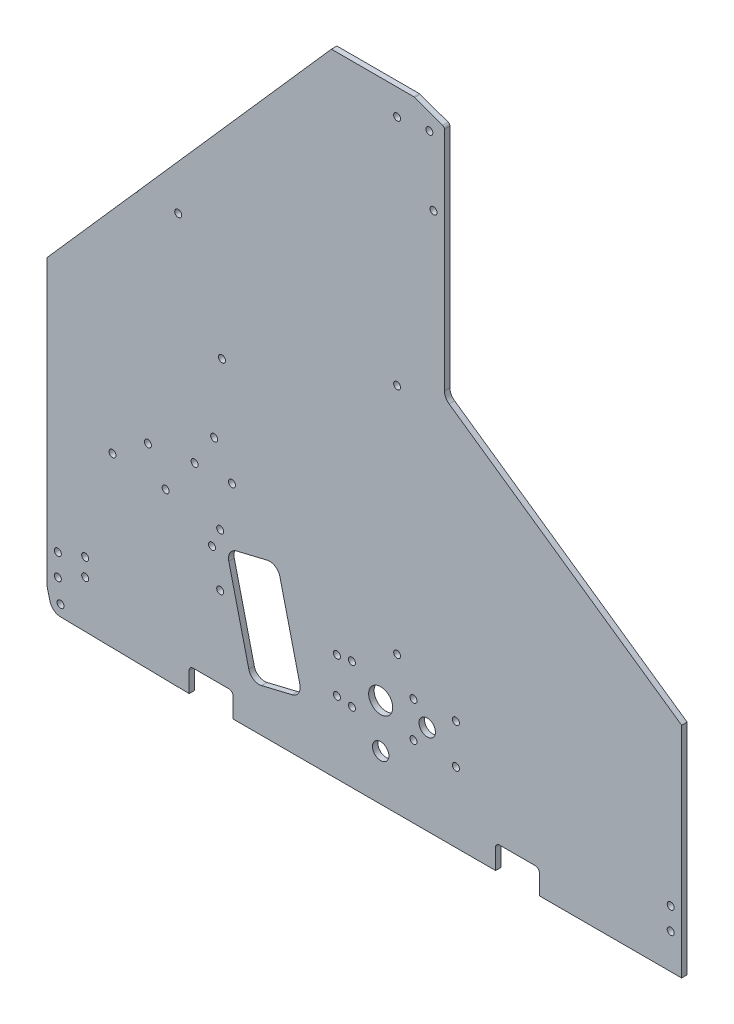
SolidWorks part; units mm, degrees
ref_plane "Front Plane" through (0, 0, 0) normal (0, 0, 1) x (1, 0, 0)
ref_plane "Top Plane" through (0, 0, 0) normal (0, 1, 0) x (1, 0, 0)
ref_plane "Right Plane" through (0, 0, 0) normal (1, 0, 0) x (0, 0, -1)
sketch "Sketch1" plane through (0, 0, 0) normal (0, 0, 1) x (1, 0, 0)
  line L0 (82.55, -20.32) -> (82.55, -6.35)
  line L2 (0, 0) -> (0, 157.48)
  line L4 (368.3, -20.32) -> (368.3, 106.68)
  line L5 (82.55, -6.35) -> (107.95, -6.35)
  line L6 (107.95, -6.35) -> (107.95, -20.32)
  line L7 (107.95, -20.32) -> (260.35, -20.32)
  line L8 (260.35, -20.32) -> (260.35, -6.35)
  line L9 (260.35, -6.35) -> (285.75, -6.35)
  line L10 (285.75, -6.35) -> (285.75, -20.32)
  line L11 (285.75, -20.32) -> (368.3, -20.32)
  line L12 (361.95, 12.7) -> (368.3, 12.7) construction
  line L13 (0, 0) -> (6.35, 0) construction
  line L14 (0.1896, -7.8901) -> (1.7771, -14.2401)
  line L15 (7.8295, -19.0491) -> (82.55, -20.32)
  line L16 (0, 0) -> (0, -6.35)
  line L17 (85.725, 97.155) -> (82.9754, 95.5675) construction
  line L18 (97.0634, 115.6163) -> (58.5686, 93.3913) construction
  line L19 (97.0634, 115.6163) -> (107.3822, 97.7437) construction
  line L20 (58.5686, 93.3913) -> (68.8873, 75.5187) construction
  line L21 (107.3822, 97.7437) -> (68.8873, 75.5187) construction
  line L22 (97.0634, 115.6163) -> (68.8873, 75.5187) construction
  line L23 (58.5686, 93.3913) -> (107.3822, 97.7437) construction
  line L24 (7.9375, -12.7) -> (95.7973, 60.4105) construction
  line L25 (203.2, 59.805) -> (203.2, 194.805) construction
  line L26 (203.2, 194.805) -> (203.2, 329.805) construction
  line L27 (355.6, 332.105) -> (330.2, 332.105) construction
  line L28 (330.2, 332.105) -> (330.2, 217.805) construction
  line L29 (330.2, 217.805) -> (355.6, 217.805) construction
  line L30 (355.6, 217.805) -> (355.6, 332.105) construction
  line L31 (203.2, 344.805) -> (203.2, 194.805) construction
  line L32 (50.8, 332.105) -> (76.2, 332.105) construction
  line L33 (76.2, 332.105) -> (76.2, 217.805) construction
  line L34 (50.8, 217.805) -> (50.8, 332.105) construction
  line L35 (76.2, 217.805) -> (50.8, 217.805) construction
  line L36 (213.2, 344.805) -> (230.6638, 338.455)
  line L37 (203.2, 344.805) -> (165.1, 344.805)
  line L38 (203.2, 344.805) -> (213.2, 344.805)
  line L39 (348.5362, 344.805) -> (413.4623, 344.805)
  line L40 (348.5362, 344.805) -> (230.6638, 344.805) construction
  line L42 (165.1, 344.805) -> (0, 157.48)
  line L44 (230.6638, 338.455) -> (230.6638, 202.565)
  line L45 (230.6638, 202.565) -> (368.3, 106.68)
  line L46 (213.2, 344.805) -> (-141.0713, 344.805) construction
  circle A0 centre (6.35, 0) radius 2.032
  circle A1 centre (6.35, 12.7) radius 2.032
  circle A2 centre (361.95, 0) radius 2.032
  circle A3 centre (361.95, 12.7) radius 2.032
  arc A5 (1.7771, -14.2401) -> (7.8295, -19.0491) centre (7.9375, -12.7) ccw
  circle A6 centre (7.9375, -12.7) radius 2.032
  arc A7 (0, -6.35) -> (0.1896, -7.8901) centre (6.35, -6.35) ccw
  circle A8 centre (38.1, 78.105) radius 2.032
  circle A9 centre (85.725, 97.155) radius 2.032
  circle A10 centre (58.5686, 93.3913) radius 2.032
  circle A11 centre (68.8873, 75.5187) radius 2.032
  circle A12 centre (107.3822, 97.7437) radius 2.032
  circle A13 centre (97.0634, 115.6163) radius 2.032
  circle A14 centre (95.7973, 60.4105) radius 2.032
  circle A15 centre (203.2, 59.805) radius 2
  circle A16 centre (203.2, 194.805) radius 2
  circle A17 centre (203.2, 329.805) radius 2
  circle A18 centre (63.5, 313.055) radius 2.032
  circle A19 centre (101.6, 157.48) radius 2.032
  circle A20 centre (355.6, 332.105) radius 2.032
  circle A21 centre (330.2, 332.105) radius 2.032
  circle A22 centre (355.6, 217.805) radius 2.032
  circle A23 centre (330.2, 217.805) radius 2.032
  circle A24 centre (50.8, 332.105) radius 2.032
  circle A25 centre (76.2, 332.105) radius 2.032
  circle A26 centre (50.8, 217.805) radius 2.032
  circle A27 centre (76.2, 217.805) radius 2.032
  circle A28 centre (221.9319, 332.105) radius 2
  circle A29 centre (224.3138, 293.243) radius 2.032
  point P82 (203.2, 344.805)
  point P83 (221.9319, 341.63)
  dimension "D6" = 4.064
  dimension "D10" = 6.35
  dimension "D11" = 4.064
  dimension "D17" = 38.1
  dimension "D27" = 4
  dimension "D31" = 4.064
  dimension "D32" = 38.1
  dimension "D36" = 4.064
  dimension "D47" = 45.212
  dimension "D48" = 4.064
  dimension "D2" = 127
  dimension "D3" = 13.97
  dimension "D4" = 25.4
  dimension "D5" = 152.4
  dimension "D7" = 12.7
  dimension "D8" = 6.35
  dimension "D9" = 20.32
  dimension "D12" = 12.7
  dimension "D13" = 1.5875
  dimension "D14" = 82.55
  dimension "D15" = 368.3
  dimension "D16" = 6.35
  dimension "D18" = 98.425
  dimension "D19" = 47.625
  dimension "D20" = 19.05
  dimension "D21" = 3.175
  dimension "D22" = 60
  dimension "D23" = 20.6375
  dimension "D24" = 44.45
  dimension "D25" = 38.1
  dimension "D26" = 114.3
  dimension "D28" = 135
  dimension "D29" = 12.7
  dimension "D30" = 15
  dimension "D33" = 63.5
  dimension "D34" = 27.4638
  dimension "D35" = 101.6
  dimension "D37" = 114.3
  dimension "D38" = 25.4
  dimension "D39" = 12.7
  dimension "D40" = 157.48
  dimension "D41" = 142.24
  dimension "D42" = 365.125
  dimension "D43" = 10
  dimension "D44" = 6.35
  dimension "D45" = 31.75
  dimension "D46" = 6.35
  dimension "D49" = 6.35
  dimension "D50" = 203.2
extrude "Boss-Extrude1" add sketch "Sketch1" along normal blind 3.175 contours L16 A7 L14 A5 L15 L2 A0 A1 A6 region at (171.6133, 119.1447, 0)
fillet "Fillet1" radius 2.286 4 edges at (285.75, -6.35, 1.5875) (107.95, -6.35, 1.5875) (260.35, -6.35, 1.5875) (82.55, -6.35, 1.5875)
fillet "Fillet2" radius 6.35 1 edges at (230.6638, 202.565, 1.5875)
sketch "Sketch2" plane through (0, 0, 0) normal (0, 0, -1) x (-1, 0, 0)
  circle A0 centre (-100.5528, 71.086) radius 2.032 construction
  circle A1 centre (-100.5528, 40.606) radius 2.032 construction
  circle A2 centre (-22.225, 18.2025) radius 2.032 construction
  circle A3 centre (-22.225, 8.0425) radius 2.032 construction
  circle A4 centre (-100.5528, 71.086) radius 2.032
  circle A5 centre (-100.5528, 40.606) radius 2.032
  circle A6 centre (-22.225, 18.2025) radius 2.032
  circle A7 centre (-22.225, 8.0425) radius 2.032
extrude "Cut-Extrude1" cut sketch "Sketch2" against normal through all
fillet "Fillet3" radius 1.5875 2 edges at (230.6638, 338.455, 1.5875) (213.2, 344.805, 1.5875)
sketch "Sketch3" plane through (0, 0, 3.175) normal (0, 0, 1) x (1, 0, 0)
  line L0 (132.9524, 63.2646) -> (132.7215, 64.2281) construction
  line L1 (128.3814, 66.8897) -> (110.6828, 62.6472) construction
  line L2 (114.5132, 58.4237) -> (126.8822, 61.3887) construction
  line L3 (108.0212, 58.3071) -> (108.2522, 57.3436) construction
  line L4 (131.2006, 57.703) -> (140.0164, 20.9265) construction
  line L5 (144.0993, 16.7636) -> (132.9524, 63.2646) construction
  line L6 (108.2522, 57.3436) -> (119.3991, 10.8426) construction
  line L7 (121.1509, 16.4042) -> (112.3351, 53.1807) construction
  line L8 (119.3991, 10.8426) -> (119.6301, 9.8791) construction
  line L9 (144.3303, 15.8001) -> (144.0993, 16.7636) construction
  line L10 (137.8383, 15.6835) -> (125.4694, 12.7185) construction
  line L11 (123.9701, 7.2175) -> (141.6687, 11.4601) construction
  line L12 (132.9524, 63.2646) -> (132.7215, 64.2281)
  line L13 (128.3814, 66.8897) -> (110.6828, 62.6472)
  line L14 (114.5132, 58.4237) -> (126.8822, 61.3887)
  line L15 (108.0212, 58.3071) -> (108.2522, 57.3436)
  line L16 (131.2006, 57.703) -> (140.0164, 20.9265)
  line L17 (144.0993, 16.7636) -> (132.9524, 63.2646)
  line L18 (108.2522, 57.3436) -> (119.3991, 10.8426)
  line L19 (121.1509, 16.4042) -> (112.3351, 53.1807)
  line L20 (119.3991, 10.8426) -> (119.6301, 9.8791)
  line L21 (144.3303, 15.8001) -> (144.0993, 16.7636)
  line L22 (137.8383, 15.6835) -> (125.4694, 12.7185)
  line L23 (123.9701, 7.2175) -> (141.6687, 11.4601)
  line L24 (127.7894, 69.3598) -> (110.0908, 65.1172)
  line L25 (105.5512, 57.715) -> (105.7822, 56.7515)
  line L26 (105.7822, 56.7515) -> (116.9291, 10.2505)
  line L27 (116.9291, 10.2505) -> (117.16, 9.287)
  line L28 (124.5622, 4.7475) -> (142.2608, 8.99)
  line L29 (146.8003, 16.3922) -> (146.5694, 17.3557)
  line L30 (146.5694, 17.3557) -> (135.4225, 63.8567)
  line L31 (135.4225, 63.8567) -> (135.1915, 64.8202)
  arc A0 (132.7215, 64.2281) -> (128.6308, 66.9403) centre (129.2206, 63.3889) ccw construction
  arc A1 (110.6828, 62.6472) -> (110.4377, 62.5791) centre (111.522, 59.1463) ccw construction
  arc A2 (128.6308, 66.9403) -> (128.3814, 66.8897) centre (129.2206, 63.3889) ccw construction
  arc A3 (110.4377, 62.5791) -> (108.0212, 58.3071) centre (111.522, 59.1463) ccw construction
  arc A4 (119.6301, 9.8791) -> (123.7207, 7.1669) centre (123.1309, 10.7183) ccw construction
  arc A5 (141.9139, 11.5281) -> (144.3303, 15.8001) centre (140.8295, 14.9609) ccw construction
  arc A6 (141.6687, 11.4601) -> (141.9139, 11.5281) centre (140.8295, 14.9609) ccw construction
  arc A7 (123.7207, 7.1669) -> (123.9701, 7.2175) centre (123.1309, 10.7183) ccw construction
  arc A8 (132.7215, 64.2281) -> (128.6308, 66.9403) centre (129.2206, 63.3889) ccw
  arc A9 (110.6828, 62.6472) -> (110.4377, 62.5791) centre (111.522, 59.1463) ccw
  arc A10 (128.6308, 66.9403) -> (128.3814, 66.8897) centre (129.2206, 63.3889) ccw
  arc A11 (110.4377, 62.5791) -> (108.0212, 58.3071) centre (111.522, 59.1463) ccw
  arc A12 (119.6301, 9.8791) -> (123.7207, 7.1669) centre (123.1309, 10.7183) ccw
  arc A13 (141.9139, 11.5281) -> (144.3303, 15.8001) centre (140.8295, 14.9609) ccw
  arc A14 (141.6687, 11.4601) -> (141.9139, 11.5281) centre (140.8295, 14.9609) ccw
  arc A15 (123.7207, 7.1669) -> (123.9701, 7.2175) centre (123.1309, 10.7183) ccw
  arc A16 (110.0908, 65.1172) -> (109.6726, 65.0012) centre (111.522, 59.1463) ccw
  arc A17 (109.6726, 65.0012) -> (105.5512, 57.715) centre (111.522, 59.1463) ccw
  arc A18 (117.16, 9.287) -> (124.1369, 4.6613) centre (123.1309, 10.7183) ccw
  arc A19 (124.1369, 4.6613) -> (124.5622, 4.7475) centre (123.1309, 10.7183) ccw
  arc A20 (142.2608, 8.99) -> (142.6789, 9.1061) centre (140.8295, 14.9609) ccw
  arc A21 (142.6789, 9.1061) -> (146.8003, 16.3922) centre (140.8295, 14.9609) ccw
  arc A22 (135.1915, 64.8202) -> (128.2147, 69.446) centre (129.2206, 63.3889) ccw
  arc A23 (128.2147, 69.446) -> (127.7894, 69.3598) centre (129.2206, 63.3889) ccw
  ellipse E0 centre (124.5974, 48.8487) end of major axis (128.5376, 61.3578) minor radius 6 (131.2006, 57.703) -> (126.8822, 61.3887) ccw construction
  ellipse E1 centre (122.2349, 48.2824) end of major axis (113.0518, 57.6456) minor radius 6 (114.5132, 58.4237) -> (112.3351, 53.1807) ccw construction
  ellipse E2 centre (127.7541, 25.2585) end of major axis (131.6942, 37.7675) minor radius 6 (121.1509, 16.4042) -> (125.4694, 12.7185) ccw construction
  ellipse E3 centre (130.1166, 25.8248) end of major axis (139.2998, 16.4616) minor radius 6 (137.8383, 15.6835) -> (140.0164, 20.9265) ccw construction
  ellipse E4 centre (124.5974, 48.8487) end of major axis (128.5376, 61.3578) minor radius 6 (131.2006, 57.703) -> (126.8822, 61.3887) ccw
  ellipse E5 centre (122.2349, 48.2824) end of major axis (131.4181, 38.9192) minor radius 6 (114.5132, 58.4237) -> (112.3351, 53.1807) ccw
  ellipse E6 centre (127.7541, 25.2585) end of major axis (123.8139, 12.7495) minor radius 6 (121.1509, 16.4042) -> (125.4694, 12.7185) ccw
  ellipse E7 centre (130.1166, 25.8248) end of major axis (139.2998, 16.4616) minor radius 6 (137.8383, 15.6835) -> (140.0164, 20.9265) ccw
  dimension "D1" = 2.54
extrude "Cut-Extrude2" cut sketch "Sketch3" against normal through all contours A22 A23 L24 A16 A17 L25 L26 L27 A18 A19 L28 A20 A21 L29 L30 L31 A15 A12 L20 L18 L15 A11 A9 L13 A10 A8 L12 L17 L21 A13 A14 L23 | A12 A15 L23 A14 A13 L21 L17 L12 A8 A10 L13 A9 A11 L15 L18 L20 E7 L22 E6 L19 E5 L14 E4 L16 | L22 E7 L16 E4 L14 E5 L19 E6 region at (137.844, 39.8506, 3.175) region at (126.1758, 37.0536, 3.175) region at (128.1544, 68.6507, 3.175)
sketch "Sketch4" plane through (0, 0, 3.175) normal (0, 0, 1) x (1, 0, 0)
  line L0 (107.3822, 97.7437) -> (68.8873, 75.5187) construction
  line L1 (168.275, 21.4312) -> (212.725, 21.4312) construction
  line L2 (168.275, 21.4312) -> (168.275, 42.0687) construction
  line L3 (168.275, 42.0687) -> (212.725, 42.0687) construction
  line L4 (212.725, 21.4312) -> (212.725, 42.0687) construction
  line L5 (168.275, 21.4312) -> (212.725, 42.0687) construction
  line L6 (168.275, 42.0687) -> (212.725, 21.4312) construction
  line L7 (97.0634, 115.6163) -> (107.3822, 97.7437) construction
  line L8 (107.95, -20.32) -> (260.35, -20.32) construction
  line L9 (193.675, 31.75) -> (177.005, 31.75) construction
  line L10 (190.5, 31.75) -> (193.675, 31.75) construction
  line L11 (6.35, 12.7) -> (361.95, 12.7) construction
  line L12 (107.95, -6.35) -> (107.95, -20.32) construction
  line L13 (193.675, 31.75) -> (220.6625, 31.75) construction
  line L14 (177.005, 20.2819) -> (177.005, 43.2181) construction
  line L15 (213.2, 44.805) -> (193.2, 44.805) construction
  line L16 (213.2, 44.805) -> (213.2, 344.805) construction
  line L17 (213.2, 344.805) -> (193.2, 344.805) construction
  line L18 (193.2, 44.805) -> (193.2, 344.805) construction
  line L19 (213.2, 44.805) -> (193.2, 344.805) construction
  line L20 (213.2, 344.805) -> (193.2, 44.805) construction
  circle A0 centre (168.275, 42.0687) radius 2.032
  circle A1 centre (212.725, 42.0687) radius 2.032
  circle A2 centre (212.725, 21.4312) radius 2.032
  circle A3 centre (168.275, 21.4312) radius 2.032
  circle A4 centre (193.675, 31.75) radius 6.985
  circle A5 centre (220.6625, 31.75) radius 4.7625
  circle A7 centre (220.6625, 31.75) radius 14.2875 construction
  circle A8 centre (193.675, 31.75) radius 12.7 construction
  circle A9 centre (177.005, 43.2181) radius 2.032
  circle A10 centre (177.005, 20.2819) radius 2.032
  circle A11 centre (237.33, 43.2181) radius 2.032
  circle A12 centre (237.33, 20.2819) radius 2.032
  circle A13 centre (193.675, 6.35) radius 4.7625
  point P0 (190.5, 31.75)
  point P26 (203.2, 194.805)
  point P38 (177.005, 31.75)
  dimension "D1" = 4.064
  dimension "D4" = 13.97
  dimension "D7" = 9.525
  dimension "D10" = 25.4
  dimension "D11" = 28.575
  dimension "D2" = 52.07
  dimension "D3" = 3.175
  dimension "D5" = 82.55
  dimension "D6" = 26.9875
  dimension "D8" = 20
  dimension "D9" = 300
  dimension "D12" = 16.67
  dimension "D13" = 22.9362
  dimension "D14" = 60.325
  dimension "D15" = 25.4
extrude "Cut-Extrude3" cut sketch "Sketch4" against normal through all
